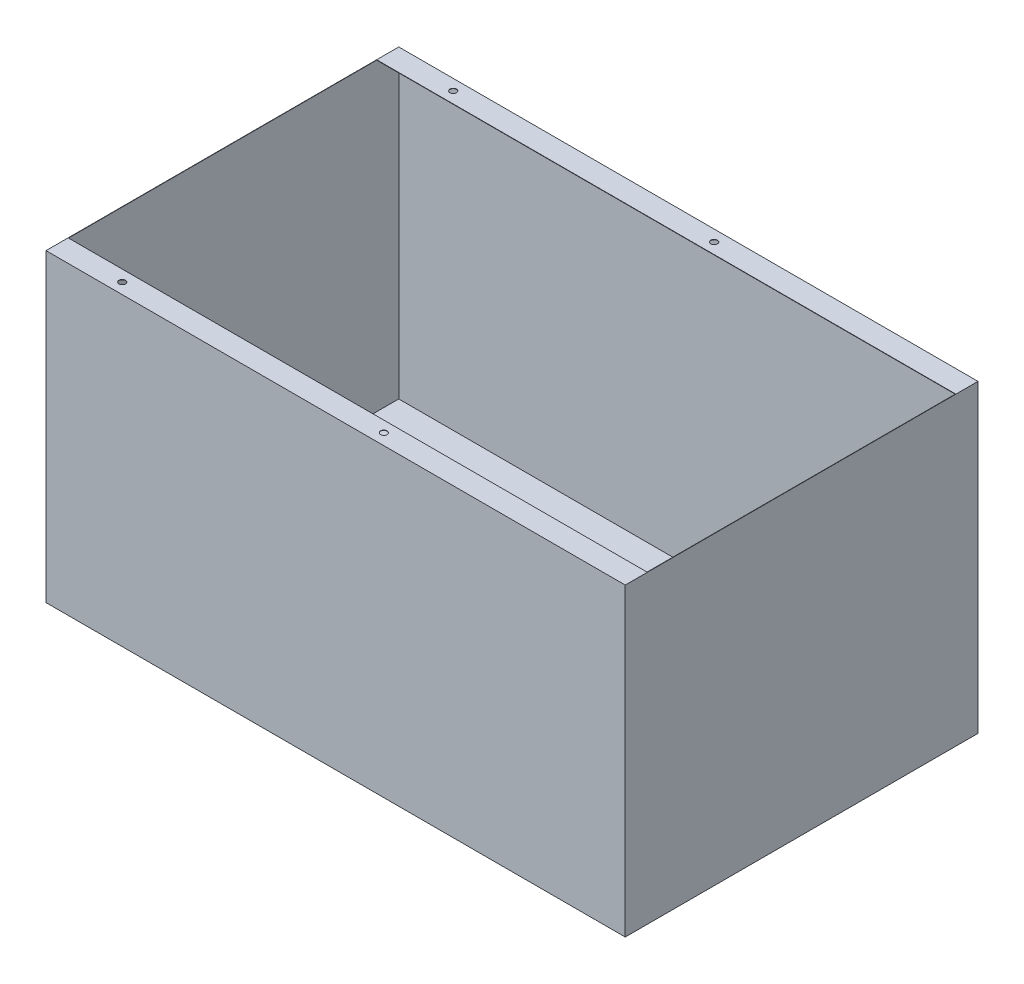
SolidWorks part; units mm, degrees
ref_plane "Front Plane" through (0, 0, 0) normal (0, 0, 1) x (1, 0, 0)
ref_plane "Top Plane" through (0, 0, 0) normal (0, 1, 0) x (1, 0, 0)
ref_plane "Right Plane" through (0, 0, 0) normal (1, 0, 0) x (0, 0, -1)
sketch "Sketch1" plane through (0, 0, 0) normal (1, 0, 0) x (0, 0, -1)
  line L1 (0, 0) -> (2057.4, 0)
  line L2 (0, 0) -> (0, 1778)
  line L3 (0, 1778) -> (2057.4, 1778)
  line L4 (2057.4, 0) -> (2057.4, 1778)
  dimension "D1" = 2057.4
  dimension "D2" = 1778
extrude "Boss-Extrude1" add sketch "Sketch1" against normal blind 3378.2
sketch "Sketch2" plane through (0, 1778, 0) normal (0, 1, 0) x (1, 0, 0)
  line L0 (-3378.2, 2057.4) -> (0, 2057.4) construction
  line L1 (-2, 2) -> (-3376.2, 2)
  line L2 (-2, 2) -> (-2, 2055.4)
  line L3 (-2, 2055.4) -> (-3376.2, 2055.4)
  line L4 (-3376.2, 2) -> (-3376.2, 2055.4)
  line L5 (-2, 2) -> (-3376.2, 2055.4) construction
  line L6 (-2, 2055.4) -> (-3376.2, 2) construction
  line L7 (0, 2057.4) -> (0, 0) construction
  line L8 (-3378.2, 0) -> (0, 0) construction
  line L9 (-3378.2, 2057.4) -> (-3378.2, 0) construction
  point P0 (-1689.1, 1028.7)
  dimension "D1" = 2
  dimension "D2" = 2
  dimension "D3" = 2
  dimension "D4" = 2
extrude "Cut-Extrude1" cut sketch "Sketch2" against normal blind 1776
sketch "Sketch3" plane through (0, 0, -2055.4) normal (0, 0, 1) x (1, 0, 0)
  line L1 (-3376.2, 1778) -> (-2, 1778)
  line L2 (-3376.2, 1778) -> (-3376.2, 1776)
  line L3 (-3376.2, 1776) -> (-2, 1776)
  line L4 (-2, 1778) -> (-2, 1776)
  dimension "D1" = 2
extrude "Boss-Extrude2" add sketch "Sketch3" along normal blind 127
sketch "Sketch4" plane through (0, 0, -2) normal (0, 0, -1) x (-1, 0, 0)
  line L1 (2, 1778) -> (3376.2, 1778)
  line L2 (2, 1778) -> (2, 1776)
  line L3 (2, 1776) -> (3376.2, 1776)
  line L4 (3376.2, 1778) -> (3376.2, 1776)
  dimension "D1" = 2
extrude "Boss-Extrude3" add sketch "Sketch4" along normal blind 127
sketch "Sketch5" plane through (0, 1778, 0) normal (0, 1, 0) x (1, 0, 0)
  line L0 (0, 2057.4) -> (0, 0) construction
  line L1 (-3376.2, 129) -> (-2, 129) construction
  line L2 (-2, 1928.4) -> (-3376.2, 1928.4) construction
  line L3 (-3378.2, 0) -> (0, 0) construction
  line L4 (-3378.2, 2057.4) -> (0, 2057.4) construction
  circle A0 centre (-1473.2, 65.5) radius 19.05
  circle A1 centre (-1473.2, 1991.9) radius 19.05
  circle A2 centre (-2997.2, 1993.9) radius 19.05
  circle A3 centre (-2997.2, 63.5) radius 19.05
  dimension "D1" = 38.1
  dimension "D2" = 38.1
  dimension "D3" = 1473.2
  dimension "D4" = 63.5
  dimension "D5" = 1473.2
  dimension "D6" = 63.5
  dimension "D7" = 38.1
  dimension "D8" = 38.1
  dimension "D9" = 63.5
  dimension "D10" = 63.5
  dimension "D11" = 1524
  dimension "D12" = 1524
extrude "Cut-Extrude2" cut sketch "Sketch5" against normal up to next
